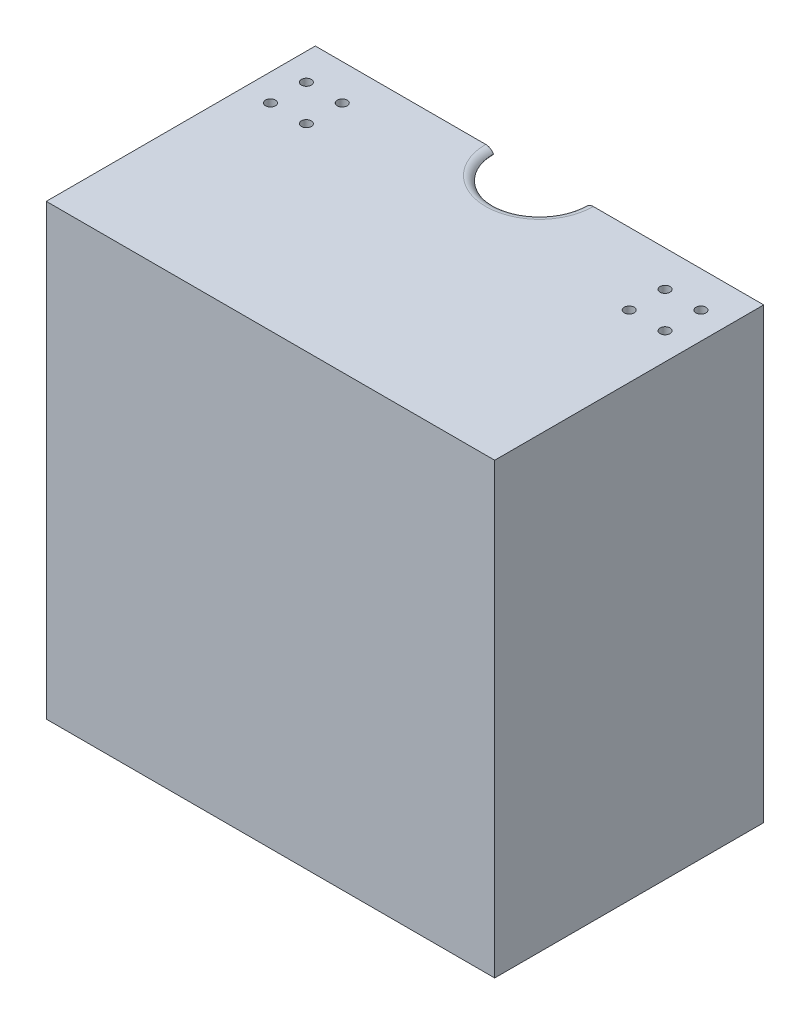
SolidWorks part; units mm, degrees
ref_plane "Front Plane" through (0, 0, 0) normal (0, 0, 1) x (1, 0, 0)
ref_plane "Top Plane" through (0, 0, 0) normal (0, 1, 0) x (1, 0, 0)
ref_plane "Right Plane" through (0, 0, 0) normal (1, 0, 0) x (0, 0, -1)
sketch "Sketch1" plane through (0, 0, 0) normal (0, 0, 1) x (1, 0, 0)
  line L1 (-63.5, 63.5) -> (63.5, 63.5)
  line L2 (-63.5, 63.5) -> (-63.5, -63.5)
  line L3 (-63.5, -63.5) -> (63.5, -63.5)
  line L4 (63.5, 63.5) -> (63.5, -63.5)
  line L5 (-63.5, 63.5) -> (63.5, -63.5) construction
  line L6 (-63.5, -63.5) -> (63.5, 63.5) construction
  point P0 (0, 0)
  dimension "D1" = 127
  dimension "D2" = 127
extrude "Boss-Extrude1" add sketch "Sketch1" along normal blind 76.2
shell "Shell2" thickness 2.54 removed face at (0, 0, 0)
sketch "Sketch2" plane through (0, 63.5, 0) normal (0, 1, 0) x (1, 0, 0)
  line L0 (63.5, 0) -> (-63.5, 0) construction
  arc A0 (-12.7, 0) -> (12.7, 0) centre (0, 0) ccw
extrude "Cut-Extrude1" cut sketch "Sketch2" against normal blind 2.54 and the other way through all
fillet "Fillet3" radius 2.54 2 edges at (0, 60.96, 12.7) (0, 63.5, 12.7)
sketch "Sketch3" plane through (0, -63.5, 0) normal (0, -1, 0) x (1, 0, 0)
  line L6 (-63.5, 76.2) -> (-63.5, 0) construction
  line L7 (-63.5, 0) -> (63.5, 0) construction
  circle A0 centre (-55.88, 20.32) radius 1.4097
  circle A1 centre (-45.72, 20.32) radius 1.4097
  circle A2 centre (-55.88, 10.16) radius 1.4097
  circle A3 centre (-45.72, 10.16) radius 1.4097
  dimension "D3" = 2.8194
  dimension "D4" = 2.8194
  dimension "D5" = 7.62
  dimension "D6" = 17.78
  dimension "D7" = 17.78
  dimension "D8" = 10.16
  dimension "D9" = 2.8194
  dimension "D10" = 2.8194
  dimension "D11" = 10.16
  dimension "D12" = 20.32
  dimension "D13" = 20.32
  dimension "D2" = 7.62
extrude "Cut-Extrude2" cut sketch "Sketch3" against normal through all
mirror "Mirror1" about plane through (0, 0, 0) normal (1, 0, 0) of "Cut-Extrude2"
